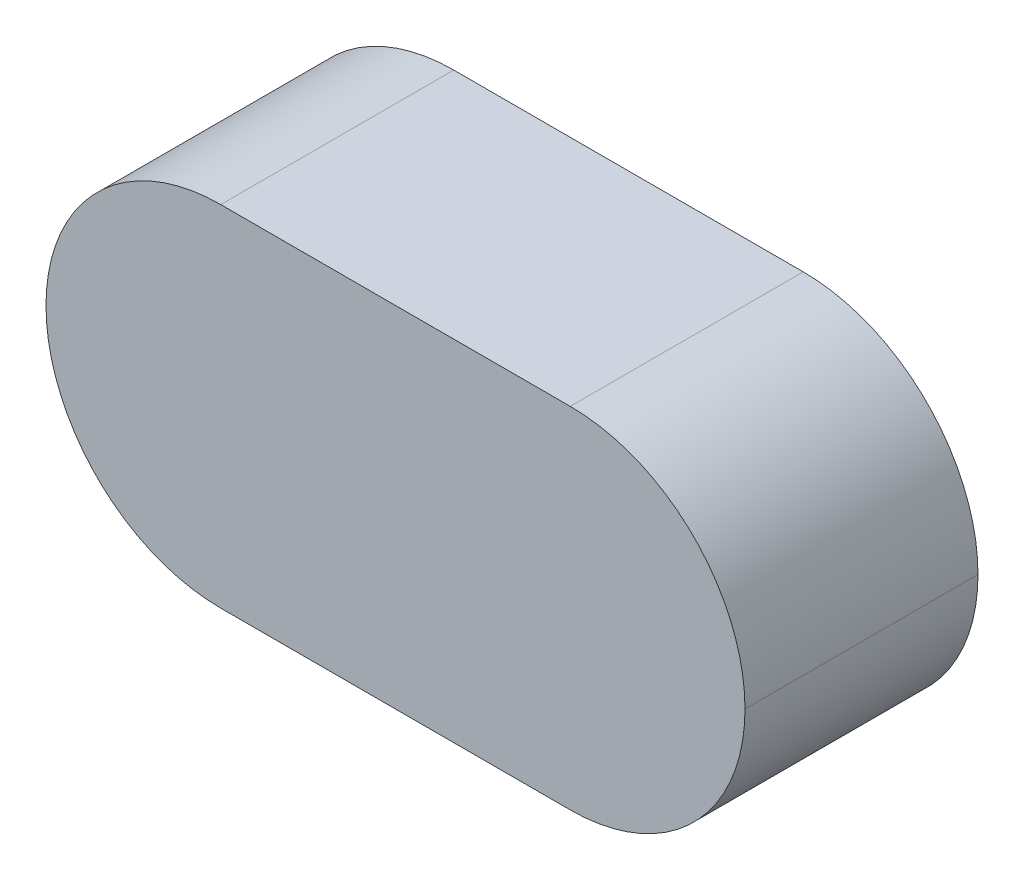
SolidWorks part; units mm, degrees
ref_plane "Front Plane" through (0, 0, 0) normal (0, 0, 1) x (1, 0, 0)
ref_plane "Top Plane" through (0, 0, 0) normal (0, 1, 0) x (1, 0, 0)
ref_plane "Right Plane" through (0, 0, 0) normal (1, 0, 0) x (0, 0, -1)
other "Configuration Table"
sketch "Sketch1" plane through (0, 0, 0) normal (0, 0, 1) x (1, 0, 0)
  line L5 (0, 0) -> (30, 0)
  line L6 (0, 0) -> (0, 15)
  line L7 (0, 15) -> (30, 15)
  line L8 (30, 0) -> (30, 15)
  dimension "D1" = 30
  dimension "D2" = 15
extrude "Boss-Extrude1" add sketch "Sketch1" along normal blind 10
fillet "Fillet1" radius 7.5 4 edges at (30, 0, 5) (30, 15, 5) (0, 0, 5) (0, 15, 5)
